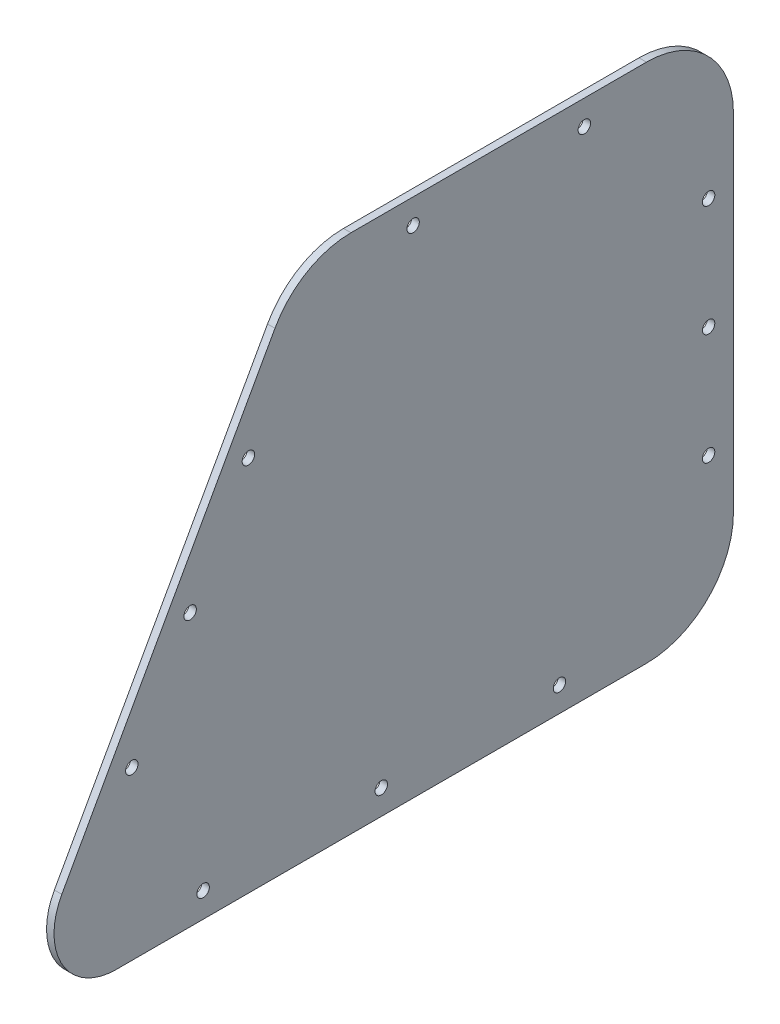
SolidWorks part; units mm, degrees
material "Acrylic (Medium-high impact)"
ref_plane "Front Plane" through (0, 0, 0) normal (0, 0, 1) x (1, 0, 0)
ref_plane "Top Plane" through (0, 0, 0) normal (0, 1, 0) x (1, 0, 0)
ref_plane "Right Plane" through (0, 0, 0) normal (1, 0, 0) x (0, 0, -1)
sketch "Sketch1" plane through (0, 0, 0) normal (1, 0, 0) x (0, 0, -1)
  line L0 (0, -1000) -> (0, 49000) construction
  line L1 (-1000, 0) -> (49000, 0) construction
  line L14 (-12.1885, 179.5) -> (106.6837, 179.5) construction
  line L15 (-29.6717, 169.2129) -> (-115.4252, 14.8564) construction
  line L16 (-106.6837, 0) -> (106.6837, 0) construction
  line L17 (126.6837, 20) -> (126.6837, 159.5) construction
  line L18 (-12.1885, 194.5) -> (106.6837, 194.5)
  line L19 (141.6837, 20) -> (141.6837, 159.5)
  line L20 (-106.6837, -15) -> (106.6837, -15)
  line L21 (-42.784, 176.4975) -> (-128.5376, 22.1411)
  arc A12 (-106.6837, 0) -> (-115.4252, 14.8564) centre (-106.6837, 10) cw construction
  arc A13 (106.6837, 0) -> (126.6837, 20) centre (106.6837, 20) ccw construction
  arc A14 (126.6837, 159.5) -> (106.6837, 179.5) centre (106.6837, 159.5) ccw construction
  arc A16 (-29.6717, 169.2129) -> (-12.1885, 179.5) centre (-12.1885, 159.5) cw construction
  arc A17 (141.6837, 159.5) -> (106.6837, 194.5) centre (106.6837, 159.5) ccw
  arc A18 (106.6837, -15) -> (141.6837, 20) centre (106.6837, 20) ccw
  arc A19 (-106.6837, -15) -> (-128.5376, 22.1411) centre (-106.6837, 10) cw
  arc A20 (-42.784, 176.4975) -> (-12.1885, 194.5) centre (-12.1885, 159.5) cw
  point P17 (47.2476, 179.5)
  point P18 (0, 0)
  dimension "D2" = 20
  dimension "D3" = 20
  dimension "D5" = 79.4361
  dimension "D1" = 10
  dimension "D4" = 20
  dimension "D6" = 213.3673
  dimension "D7" = 179.5
  dimension "D8" = 15
extrude "Boss-Extrude1" add sketch "Sketch1" along normal blind 3
sketch "Sketch2" plane through (3, 0, 0) normal (1, 0, 0) x (0, 0, -1)
  line L4 (-34.0424, 171.6411) -> (-119.796, 17.2846)
  line L5 (-34.0424, 171.6411) -> (-119.796, 17.2846) construction
  line L6 (-106.6837, -5) -> (106.6837, -5)
  line L7 (-106.6837, -5) -> (106.6837, -5) construction
  line L8 (131.6837, 20) -> (131.6837, 159.5)
  line L9 (131.6837, 20) -> (131.6837, 159.5) construction
  line L10 (106.6837, 184.5) -> (-12.1885, 184.5)
  line L11 (106.6837, 184.5) -> (-12.1885, 184.5) construction
  arc A4 (-12.1885, 184.5) -> (-34.0424, 171.6411) centre (-12.1885, 159.5) ccw
  arc A5 (-12.1885, 184.5) -> (-34.0424, 171.6411) centre (-12.1885, 159.5) ccw construction
  arc A6 (-119.796, 17.2846) -> (-106.6837, -5) centre (-106.6837, 10) ccw
  arc A7 (-119.796, 17.2846) -> (-106.6837, -5) centre (-106.6837, 10) ccw construction
  arc A8 (106.6837, -5) -> (131.6837, 20) centre (106.6837, 20) ccw
  arc A9 (106.6837, -5) -> (131.6837, 20) centre (106.6837, 20) ccw construction
  arc A10 (131.6837, 159.5) -> (106.6837, 184.5) centre (106.6837, 159.5) ccw
  arc A11 (131.6837, 159.5) -> (106.6837, 184.5) centre (106.6837, 159.5) ccw construction
  circle A32 centre (81.6837, 184.5) radius 2.5
  circle A33 centre (12.8115, 184.5) radius 2.5
  circle A34 centre (131.6837, 134.5) radius 2.5
  circle A35 centre (131.6837, 89.75) radius 2.5
  circle A44 centre (131.6837, 44.9999) radius 2.5
  circle A45 centre (71.6837, -5) radius 2.5
  circle A46 centre (0, -5) radius 2.5
  circle A47 centre (-71.6837, -5) radius 2.5
  circle A48 centre (-100.3703, 52.2509) radius 2.5
  circle A49 centre (-76.9192, 94.4629) radius 2.5
  circle A50 centre (-53.4682, 136.6748) radius 2.5
  point P1 (0, 0)
  point P3 (0, 0)
  point P4 (0, 0)
  point P7 (0, 0)
  point P8 (0, 0)
  point P11 (0, 0)
  point P13 (0, 0)
  point P15 (0, 0)
  point P19 (0, 0)
  point P23 (0, 0)
  point P25 (0, 0)
  dimension "D4" = 25
  dimension "D6" = 24.9999
  dimension "D7" = 35
  dimension "D8" = 35
  dimension "D9" = 40
  dimension "D10" = 40
  dimension "D2" = 5
  dimension "D5" = 25
  dimension "D3" = 25
  dimension "D1" = 10
extrude "Cut-Extrude1" cut sketch "Sketch2" against normal up to next
